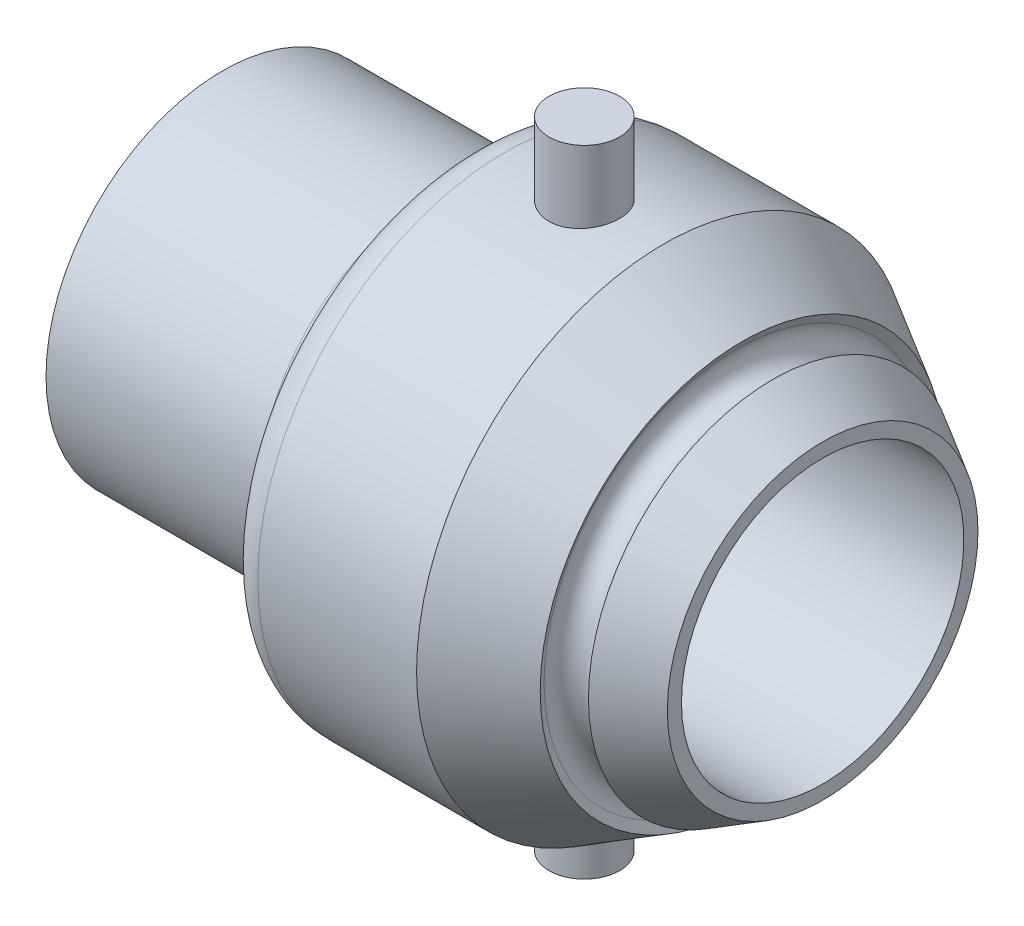
SolidWorks part; units mm, degrees
material "Сталь 12Х18Н9 ГОСТ 5632-72"
ref_plane "Front Plane" through (0, 0, 0) normal (0, 0, 1) x (1, 0, 0)
ref_plane "Top Plane" through (0, 0, 0) normal (0, 1, 0) x (1, 0, 0)
ref_plane "Right Plane" through (0, 0, 0) normal (1, 0, 0) x (0, 0, -1)
sketch "Sketch1" plane through (0, 0, 0) normal (0, 0, 1) x (1, 0, 0)
  line L0 (-10.818, 35) -> (-38.3014, 35)
  line L3 (-38.3014, 35) -> (-38.3014, 20)
  line L4 (1.6986, 26.0415) -> (2.4486, 27.3405) construction
  line L5 (11.6986, 22) -> (11.6986, 20)
  line L6 (11.6986, 20) -> (-38.3014, 20)
  line L7 (-0.4664, 27.2915) -> (0.2836, 28.5905)
  line L8 (3.8637, 24.7915) -> (4.6137, 26.0905)
  line L22 (-10.818, 35) -> (0.2836, 28.5905)
  line L24 (4.6137, 26.0905) -> (11.6986, 22)
  line L26 (-10.8231, 0) -> (10.295, 0) construction
  arc A0 (-0.4664, 27.2915) -> (3.8637, 24.7915) centre (1.6986, 26.0415) ccw
  dimension "D6" = 5
  dimension "D2" = 15
  dimension "D3" = 2
  dimension "D4" = 35
  dimension "D5" = 50
  dimension "D7" = 1.5
  dimension "D8" = 10
revolve "Revolve1" add sketch "Sketch1" angle 360 about L26
ref_plane "Plane1" through (0, 42, 0) normal (0, 1, 0) x (1, 0, 0)
sketch "Sketch3" plane through (-38.3014, 0, 0) normal (-1, 0, 0) x (0, 0, 1)
  circle A0 centre (0, 0) radius 20 construction
  circle A1 centre (0, 0) radius 20
  circle A2 centre (0, 0) radius 25
  dimension "D1" = 5
extrude "Boss-Extrude2" add sketch "Sketch3" along normal blind 35
fillet "Fillet1" radius 5 2 edges at (-38.3014, 0, -25) (-38.3014, 0, 35)
sketch "Sketch2" plane through (0, 42, 0) normal (0, 1, 0) x (1, 0, 0)
  line L0 (-33.3014, 0) -> (-10.818, 0) construction
  line L1 (-22.0597, 35) -> (-22.0597, -35) construction
  line L2 (-10.818, 35) -> (-33.3014, 35) construction
  line L3 (-33.3014, -35) -> (-10.818, -35) construction
  line L5 (-10.818, -35) -> (-10.818, 35) construction
  line L6 (-33.3014, 35) -> (-33.3014, -35) construction
  circle A0 centre (-22.0597, 0) radius 5
  dimension "D1" = 10
extrude "Boss-Extrude1" add sketch "Sketch2" against normal up to body and the other way blind 3 separate body
mirror "Mirror1" about plane through (0, 0, 0) normal (0, 1, 0) of "Boss-Extrude1"
